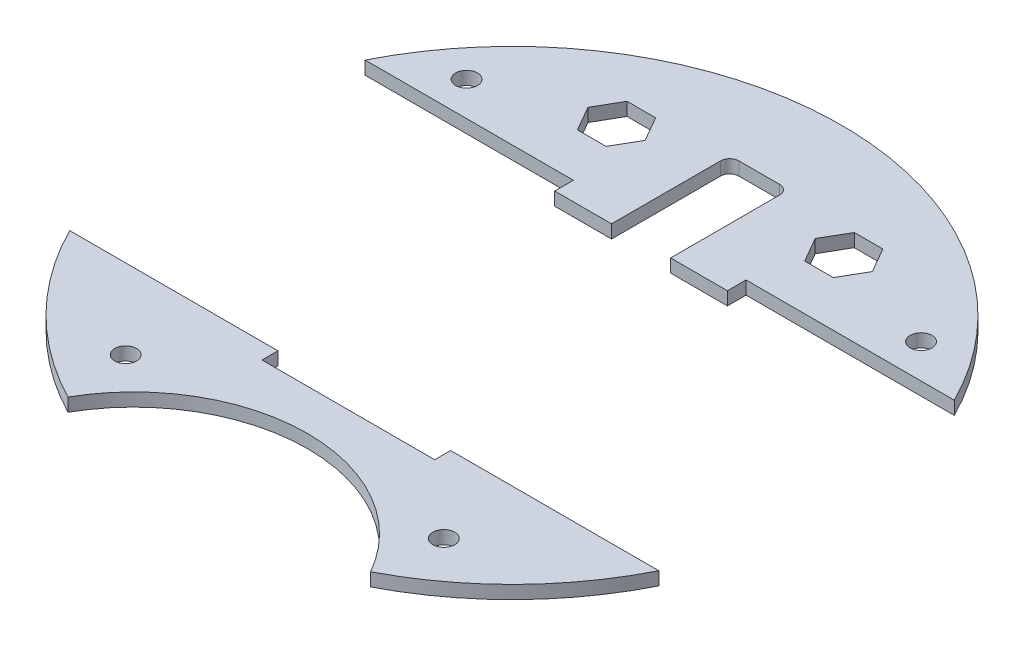
SolidWorks part; units mm, degrees
material "Acrylic (Medium-high impact)"
ref_plane "Front Plane" through (0, 0, 0) normal (0, 0, 1) x (1, 0, 0)
ref_plane "Top Plane" through (0, 0, 0) normal (0, 1, 0) x (1, 0, 0)
ref_plane "Right Plane" through (0, 0, 0) normal (1, 0, 0) x (0, 0, -1)
sketch "Sketch1" plane through (0, 0, 0) normal (0, 1, 0) x (1, 0, 0)
  line L0 (0, -83.2398) -> (-33.2911, -64.4046) construction
  line L1 (0, -83.2398) -> (0, 0) construction
  arc A0 (33.2911, -64.4046) -> (-33.2911, -64.4046) centre (0, 0) ccw
  arc A1 (33.2911, -64.4046) -> (-33.2911, -64.4046) centre (0, -83.2398) ccw
  dimension "D1" = 145
  dimension "D2" = 76.5
  dimension "D3" = 60.5
extrude "Boss-Extrude1" add sketch "Sketch1" along normal blind 2.9
sketch "solenoid placement" plane through (0, 2.9, 0) normal (0, 1, 0) x (1, 0, 0)
  line L4 (-19, -36) -> (19, -36)
  line L5 (-19, 28.4) -> (-19, -36)
  line L6 (19, 28.4) -> (-19, 28.4)
  line L7 (19, -36) -> (19, 28.4)
  line L8 (-19, -36) -> (19, -36)
  line L9 (-19, 28.4) -> (-19, -36)
  line L10 (19, 28.4) -> (-19, 28.4)
  line L11 (19, -36) -> (19, 28.4)
  dimension "D1" = 0
extrude "Cut-Extrude1" cut sketch "solenoid placement" against normal through all
sketch "Sketch4" plane through (0, 2.9, 0) normal (0, 1, 0) x (1, 0, 0)
  line L4 (-6.5, 28.1) -> (6.5, 28.1)
  line L5 (6.5, 28.1) -> (6.5, 52.4)
  line L6 (4.5, 54.4) -> (-4.5, 54.4)
  line L7 (-6.5, 52.4) -> (-6.5, 28.1)
  line L8 (-6.5, 28.1) -> (6.5, 28.1)
  line L9 (6.5, 28.1) -> (6.5, 52.4)
  line L10 (4.5, 54.4) -> (-4.5, 54.4)
  line L11 (-6.5, 52.4) -> (-6.5, 28.1)
  arc A2 (6.5, 52.4) -> (4.5, 54.4) centre (4.5, 52.4) ccw
  arc A3 (-4.5, 54.4) -> (-6.5, 52.4) centre (-4.5, 52.4) ccw
  arc A4 (6.5, 52.4) -> (4.5, 54.4) centre (4.5, 52.4) ccw
  arc A5 (-4.5, 54.4) -> (-6.5, 52.4) centre (-4.5, 52.4) ccw
  dimension "D1" = 0
extrude "Cut-Extrude4" cut sketch "Sketch4" against normal through all
sketch "Sketch5" plane through (0, 2.9, 0) normal (0, 1, 0) x (1, 0, 0)
  line L6 (-18.7069, 48) -> (-21.8534, 53.45)
  line L7 (-21.8534, 53.45) -> (-28.1466, 53.45)
  line L8 (-28.1466, 53.45) -> (-31.2931, 48)
  line L9 (-31.2931, 48) -> (-28.1466, 42.55)
  line L10 (-28.1466, 42.55) -> (-21.8534, 42.55)
  line L11 (-21.8534, 42.55) -> (-18.7069, 48)
  line L12 (-18.7069, 48) -> (-21.8534, 53.45)
  line L13 (-21.8534, 53.45) -> (-28.1466, 53.45)
  line L14 (-28.1466, 53.45) -> (-31.2931, 48)
  line L15 (-31.2931, 48) -> (-28.1466, 42.55)
  line L16 (-28.1466, 42.55) -> (-21.8534, 42.55)
  line L17 (-21.8534, 42.55) -> (-18.7069, 48)
  line L18 (18.7069, 48) -> (21.8534, 42.55)
  line L19 (21.8534, 53.45) -> (18.7069, 48)
  line L20 (28.1466, 53.45) -> (21.8534, 53.45)
  line L21 (31.2931, 48) -> (28.1466, 53.45)
  line L22 (28.1466, 42.55) -> (31.2931, 48)
  line L23 (21.8534, 42.55) -> (28.1466, 42.55)
  line L24 (18.7069, 48) -> (21.8534, 42.55)
  line L25 (21.8534, 53.45) -> (18.7069, 48)
  line L26 (28.1466, 53.45) -> (21.8534, 53.45)
  line L27 (31.2931, 48) -> (28.1466, 53.45)
  line L28 (28.1466, 42.55) -> (31.2931, 48)
  line L29 (21.8534, 42.55) -> (28.1466, 42.55)
  dimension "D1" = 0
  dimension "D2" = 0
extrude "Cut-Extrude5" cut sketch "Sketch5" against normal through all
sketch "Sketch6" plane through (0, 2.9, 0) normal (0, 1, 0) x (1, 0, 0)
  circle A1 centre (35, -50) radius 2.4
  circle A2 centre (35, -50) radius 2.4
  circle A3 centre (-35, -50) radius 2.4
  circle A4 centre (-35, -50) radius 2.4
  circle A5 centre (-50, 40) radius 2.4
  circle A6 centre (-50, 40) radius 2.4
  circle A7 centre (50, 40) radius 2.4
  circle A8 centre (50, 40) radius 2.4
  dimension "D1" = 0
  dimension "D2" = 0
  dimension "D3" = 0
  dimension "D4" = 0
extrude "Cut-Extrude6" cut sketch "Sketch6" against normal through all
sketch "Sketch3" plane through (0, 2.9, 0) normal (0, 1, 0) x (1, 0, 0)
  line L0 (-19, 28.4) -> (-19, 32.5)
  line L1 (72.5, -32.5) -> (-72.5, -32.5)
  line L2 (72.5, -32.5) -> (72.5, 32.5)
  line L3 (72.5, 32.5) -> (19, 32.5)
  line L4 (-72.5, -32.5) -> (-72.5, 32.5)
  line L5 (72.5, -32.5) -> (-72.5, 32.5) construction
  line L6 (72.5, 32.5) -> (-72.5, -32.5) construction
  line L7 (-19, 28.4) -> (19, 28.4)
  line L8 (19, 28.4) -> (19, 32.5)
  line L9 (-19, 32.5) -> (-72.5, 32.5)
  line L10 (-19, 28.4) -> (-19, -36) construction
  line L11 (-6.5, 28.4) -> (-19, 28.4) construction
  arc A0 (33.2911, -64.4046) -> (-33.2911, -64.4046) centre (0, 0) ccw construction
  point P0 (0, 0)
  dimension "D1" = 65
extrude "Cut-Extrude3" cut sketch "Sketch3" against normal through all
equation "\"smallPulleyTeeth\"= 15"
equation "\"largePulleyTeeth\"= 30"
equation "\"eighthThick\"= 2.9mm"
equation "\"sixteenthThick\" = 1.7mm"
equation "\"quarterThick\"=6.0mm"
equation "\"OD\" = 145mm"
equation "\"puckAngle\" = 60.5deg"
equation "\"D1@Sketch1\"=\"OD\""
equation "\"puckDiam\" = 76.5mm"
equation "\"D2@Sketch1\"=\"puckDiam\""
equation "\"D3@Sketch1\"=\"puckAngle\""
equation "\"D1@Boss-Extrude1\"=\"eighthThick\""
equation "\"axlePress\" = 5.9mm"
equation "\"press\" = 0.2mm"
equation "\"wheelClear\" = 0.3mm"
equation "\"10-32clear\" = 4.8mm"
equation "\"6-32clear\" = 3.3mm"
equation "\"8-32clear\" = 4.0mm"
equation "\"wheelHeight\" = 22mm"
equation "\"wheelWell\" = 65mm"
equation "\"D1@Sketch3\"=\"wheelWell\""
